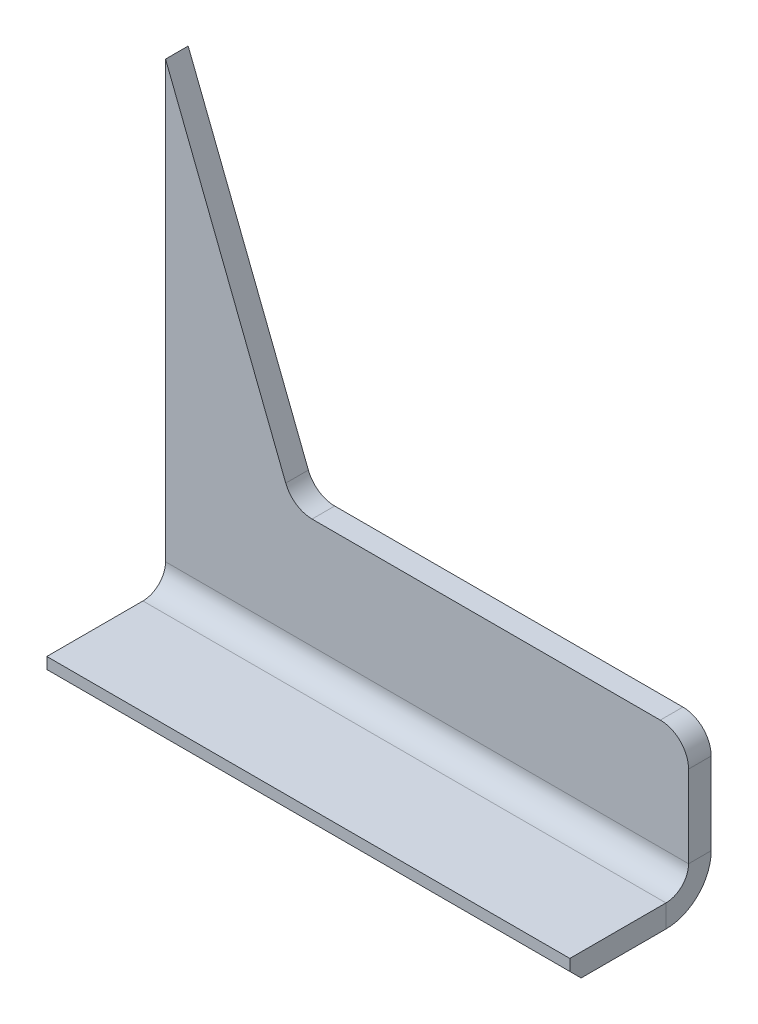
SolidWorks part; units mm, degrees
note: The reader was unsure of these and kept them because the rebuilt part matched: flange length of "边线-法兰1".
material "Q355"
ref_plane "前视基准面" through (0, 0, 0) normal (0, 0, 1) x (1, 0, 0)
ref_plane "上视基准面" through (0, 0, 0) normal (0, 1, 0) x (1, 0, 0)
ref_plane "右视基准面" through (0, 0, 0) normal (1, 0, 0) x (0, 0, -1)
sketch "草图1" plane through (0, 0, 0) normal (0, 0, 1) x (1, 0, 0)
  line L0 (0, 0) -> (45, -115)
  line L1 (45, -115) -> (185, -115)
  line L2 (185, -115) -> (185, -170)
  line L3 (0, 0) -> (0, -170)
  line L4 (0, -170) -> (185, -170)
  dimension "D1" = 55
  dimension "D2" = 185
  dimension "D3" = 170
  dimension "D4" = 140
base flange "基体-法兰1" sketch "草图1" thickness 8 reverse thickness direction no parameters "D1"=8
edge flange "边线-法兰1" sketch "草图8" flange angle 90 flange length 50 flange position material inside bend radius 8 thickness 8 relief rectangular parameters "D1"=6, "D6"=10
sketch "草图8" plane through (0, -170, 0) normal (0, -1, 0) x (1, 0, 0)
  line L2 (0, 0) -> (0, 42)
  line L3 (0, 42) -> (185, 42)
  line L4 (185, 42) -> (185, 0)
  line L7 (0, 0) -> (185, 0) construction
  line L8 (0, 0) -> (185, 0)
bend "边线折弯1" bend radius 8 bend angle 90 parameters "D5"=1
fillet "圆角1" radius 10 2 edges at (185, -115, -4) (45, -115, -4)
chamfer "倒角1" distance 4 angle 45 1 edges at (92.5, -170, 42)
sketch "折弯-线1" [suppressed] plane through (0, 0, 0) normal (0, 1, 0) x (1, 0, 0)
sketch "边界框1" [suppressed] plane through (0, 0, 0) normal (0, 1, 0) x (1, 0, 0)
sheet metal parameters "钣金6" thickness 8 parameters "D1"=8
flat pattern "平板型式6" [suppressed]
sketch "折弯-线2" plane through (0, 0, 0) normal (0, 1, 0) x (1, 0, 0)
sketch "边界框2" [suppressed] plane through (0, 0, 0) normal (0, 1, 0) x (1, 0, 0)
sheet metal parameters "钣金7" thickness 8 parameters "D1"=8
flat pattern "平板型式6"
sketch "折弯-线2" plane through (0, 0, 0) normal (0, 0, 1) x (1, 0, 0)
  line L0 (0, -163.4248) -> (185, -163.4248) construction
  line L1 (0, -163.4248) -> (185, -163.4248) construction
sketch3d "边界框2" [suppressed]
  line L0 (185, 0, 0) -> (185, -206.8496, 0) construction
  line L1 (0, 0, 0) -> (0, -206.8496, 0) construction
  line L2 (185, 0, 0) -> (0, 0, 0) construction
  line L3 (185, -206.8496, 0) -> (0, -206.8496, 0) construction
bend of the flat pattern "展开-<边线折弯1>1"
